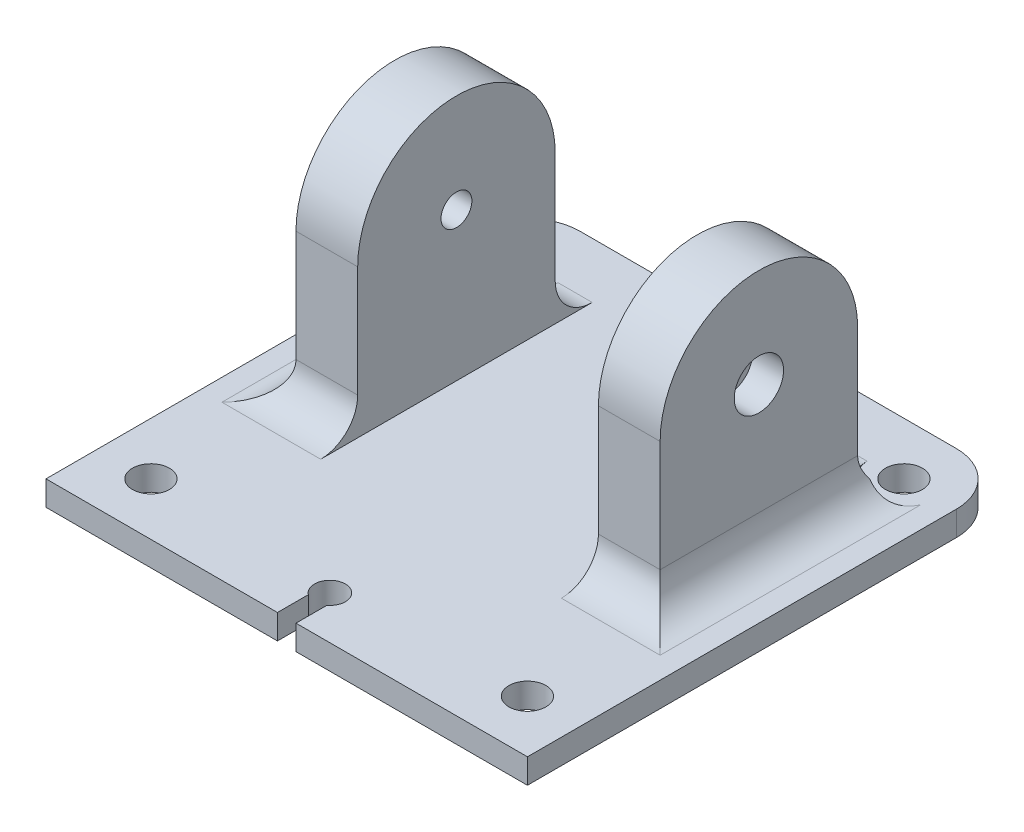
SolidWorks part; units mm, degrees
ref_plane "Front Plane" through (0, 0, 0) normal (0, 0, 1) x (1, 0, 0)
ref_plane "Top Plane" through (0, 0, 0) normal (0, 1, 0) x (1, 0, 0)
ref_plane "Right Plane" through (0, 0, 0) normal (1, 0, 0) x (0, 0, -1)
sketch "Sketch1" plane through (0, 0, 0) normal (0, 1, 0) x (1, 0, 0)
  line L0 (-19.5, 0) -> (19.5, 0) construction
  line L1 (-19.5, 19.5) -> (19.5, 19.5)
  line L2 (-19.5, 19.5) -> (-19.5, -19.5)
  line L3 (-19.5, -19.5) -> (19.5, -19.5)
  line L4 (19.5, 19.5) -> (19.5, -19.5)
  line L5 (-19.5, 19.5) -> (19.5, -19.5) construction
  line L6 (-19.5, -19.5) -> (19.5, 19.5) construction
  line L7 (0, 19.5) -> (0, -19.5) construction
  circle A0 centre (-15.25, 15.25) radius 1.5
  circle A1 centre (15.25, 15.25) radius 1.5
  circle A2 centre (15.25, -15.25) radius 1.5
  circle A3 centre (-15.25, -15.25) radius 1.5
  point P0 (0, 0)
  dimension "D3" = 3
  dimension "D1" = 39
  dimension "D2" = 39
  dimension "D4" = 30.5
extrude "Boss-Extrude1" add sketch "Sketch1" along normal blind 2
sketch "Sketch2" plane through (0, 2, 0) normal (0, 1, 0) x (1, 0, 0)
  line L0 (0, 19.5) -> (0, -19.5) construction
  line L1 (19.5, 19.5) -> (-19.5, 19.5) construction
  line L2 (-19.5, -19.5) -> (19.5, -19.5) construction
  line L3 (-19.5, 4) -> (19.5, 4) construction
  line L4 (-19.5, 0) -> (19.5, 0) construction
  line L5 (-19.5, 19.5) -> (-19.5, -19.5) construction
  line L6 (9.75, 12) -> (14.75, 12)
  line L7 (-9.75, 12) -> (-14.75, 12)
  line L8 (-9.75, 12) -> (-9.75, -4)
  line L9 (-9.75, -4) -> (-14.75, -4)
  line L10 (-14.75, 12) -> (-14.75, -4)
  line L11 (-9.75, 12) -> (-14.75, -4) construction
  line L12 (-9.75, -4) -> (-14.75, 12) construction
  line L13 (9.75, 12) -> (9.75, -4)
  line L14 (9.75, -4) -> (14.75, -4)
  line L15 (14.75, 12) -> (14.75, -4)
  line L16 (19.5, -19.5) -> (19.5, 19.5) construction
  circle A0 centre (-15.25, 15.25) radius 2.5
  point P12 (-12.25, 4)
  dimension "D5" = 5
  dimension "D1" = 19.5
  dimension "D2" = 5
  dimension "D3" = 16
  dimension "D4" = 4
extrude "Boss-Extrude2" add sketch "Sketch2" along normal blind 20 contours L7 L10 L9 L8 | L15 L6 L13 L14 region at (12.25, 2, -4) region at (-12.25, 2, -4)
sketch "Sketch3" plane through (-14.75, 0, 0) normal (-1, 0, 0) x (0, 0, 1)
  line L0 (-4, 22) -> (-4, 2) construction
  line L2 (-12, 2) -> (4, 2) construction
  line L3 (-12, 22) -> (-12, 2) construction
  line L8 (-12, 2) -> (4, 2)
  line L9 (4, 2) -> (4, 22)
  line L10 (4, 22) -> (-12, 22)
  line L11 (-12, 22) -> (-12, 2)
  line L12 (-12, 2) -> (4, 2)
  line L13 (4, 2) -> (4, 22)
  line L15 (-12, 22) -> (-12, 2)
  line L16 (4, 22) -> (-12, 22)
  circle A0 centre (-4, 14) radius 1.25
  circle A1 centre (-4, 14) radius 8
  line M4 (-12, 22) -> (-12, 2)
  line M19 (4, 22) -> (-12, 22)
  dimension "D1" = 2.5
  dimension "D2" = 0
extrude "Cut-Extrude1" cut sketch "Sketch3" against normal up to surface (29.5 mm away) contours A1 L16 M4 | A1 L13 M19 | A0 region at (-14.75, 20.2131, -10.2131) region at (-14.75, 20.2131, 2.2131) up to face at (14.75, 12, -4)
sketch "Sketch4" plane through (0, 2, 0) normal (0, 1, 0) x (1, 0, 0)
  line L0 (19.5, 19.5) -> (-19.5, 19.5) construction
  line L1 (0, 19.5) -> (0, -19.5) construction
  line L3 (-0.75, -16) -> (0.75, -16)
  line L4 (-0.75, -16) -> (-0.75, -19.5)
  line L5 (19.5, -19.5) -> (19.5, 19.5)
  line L6 (19.5, 19.5) -> (-19.5, 19.5)
  line L7 (-19.5, 19.5) -> (-19.5, -19.5)
  line L8 (-19.5, -19.5) -> (19.5, -19.5)
  line L9 (19.5, -19.5) -> (19.5, 19.5)
  line L10 (19.5, 19.5) -> (-19.5, 19.5)
  line L11 (-19.5, 19.5) -> (-19.5, -19.5)
  line L12 (-19.5, -19.5) -> (19.5, -19.5)
  line L13 (-0.75, -19.5) -> (0.75, -19.5)
  line L14 (0.75, -16) -> (0.75, -19.5)
  line L15 (-0.75, -16) -> (0.75, -19.5) construction
  line L16 (-0.75, -19.5) -> (0.75, -16) construction
  circle A0 centre (-15.25, 15.25) radius 4.25
  circle A1 centre (15.25, 15.25) radius 4.25
  circle A2 centre (0, -16) radius 1.25
  point P14 (0, -17.75)
  line M10 (19.5, 19.5) -> (-19.5, 19.5)
  line M11 (-19.5, 19.5) -> (-19.5, -19.5)
  dimension "D4" = 2.5
  dimension "D2" = 1.5
  dimension "D3" = 3.5
  dimension "D1" = 0
extrude "Cut-Extrude2" cut sketch "Sketch4" against normal up to next contours A0 L10 M11 | A1 L9 M10 | A2 | L14 L13 L4 L3 region at (-18.5507, 2, -18.5507) region at (18.5507, 2, -18.5507)
fillet "Fillet1" radius 3 6 edges at (14.75, 2, -4) (-14.75, 2, -4) (-12.25, 2, -12) (12.25, 2, -12) (12.25, 2, 4) (-12.25, 2, 4)
sketch "Sketch6" plane through (-14.75, 0, 0) normal (-1, 0, 0) x (0, 0, 1)
  circle A0 centre (-4, 14) radius 2
  dimension "D1" = 4
extrude "Cut-Extrude3" cut sketch "Sketch6" against normal blind 2.5
sketch "Sketch7" plane through (14.75, 0, 0) normal (1, 0, 0) x (0, 0, -1)
  circle A0 centre (4, 14) radius 2 construction
  circle A1 centre (4, 14) radius 2
extrude "Cut-Extrude4" cut sketch "Sketch7" against normal blind 2.5
ref_plane "Plane1" through (0, 22, 0) normal (0, 1, 0) x (1, 0, 0)
sketch "Sketch8" plane through (0, 22, 0) normal (0, 1, 0) x (1, 0, 0)
  circle A0 centre (-15.25, 15.25) radius 2.75
  circle A1 centre (15.25, 15.25) radius 2.75
  dimension "D1" = 5.5
extrude "Cut-Extrude5" cut sketch "Sketch8" against normal up to surface (20 mm away) up to face at (15.25, 2, 16.75)
